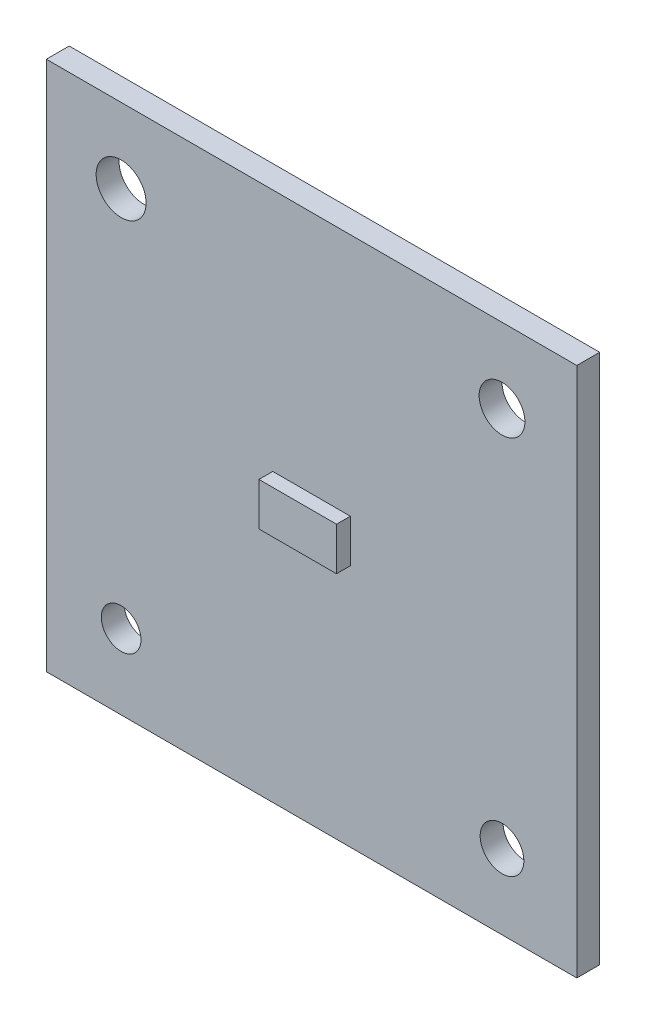
SolidWorks part; units mm, degrees
ref_plane "Front" through (0, 0, 0) normal (0, 0, 1) x (1, 0, 0)
ref_plane "Top" through (0, 0, 0) normal (0, 1, 0) x (1, 0, 0)
ref_plane "Right" through (0, 0, 0) normal (1, 0, 0) x (0, 0, -1)
sketch "Skizze1" plane through (0, 0, 0) normal (0, 0, 1) x (1, 0, 0)
  line L1 (-19.15, -19.15) -> (19.15, -19.15)
  line L2 (-19.15, -19.15) -> (-19.15, 19.15)
  line L3 (-19.15, 19.15) -> (19.15, 19.15)
  line L4 (19.15, -19.15) -> (19.15, 19.15)
  line L5 (-19.15, -19.15) -> (19.15, 19.15) construction
  line L6 (-19.15, 19.15) -> (19.15, -19.15) construction
  circle A0 centre (-13.75, 13.75) radius 1.8036
  circle A1 centre (13.75, 13.75) radius 1.6519
  circle A2 centre (13.75, -13.75) radius 1.5777
  circle A3 centre (-13.75, -13.75) radius 1.4312
  point P0 (0, 0)
  dimension "D1" = 38.3
  dimension "D2" = 27.5
extrude "Aufsatz-Linear austragen1" add sketch "Skizze1" along normal blind 1.65
sketch "Skizze2" plane through (0, 0, 1.65) normal (0, 0, 1) x (1, 0, 0)
  line L1 (-2.8, -1.55) -> (2.8, -1.55)
  line L2 (-2.8, -1.55) -> (-2.8, 1.55)
  line L3 (-2.8, 1.55) -> (2.8, 1.55)
  line L4 (2.8, -1.55) -> (2.8, 1.55)
  line L5 (-2.8, -1.55) -> (2.8, 1.55) construction
  line L6 (-2.8, 1.55) -> (2.8, -1.55) construction
  point P0 (0, 0)
  dimension "D1" = 5.6
  dimension "D2" = 3.1
extrude "Aufsatz-Linear austragen2" add sketch "Skizze2" along normal blind 1
sketch "Sketch1" plane through (0, 0, 1.65) normal (0, 0, 1) x (1, 0, 0)
  circle A0 centre (0, 0) radius 5
  dimension "D1" = 10
